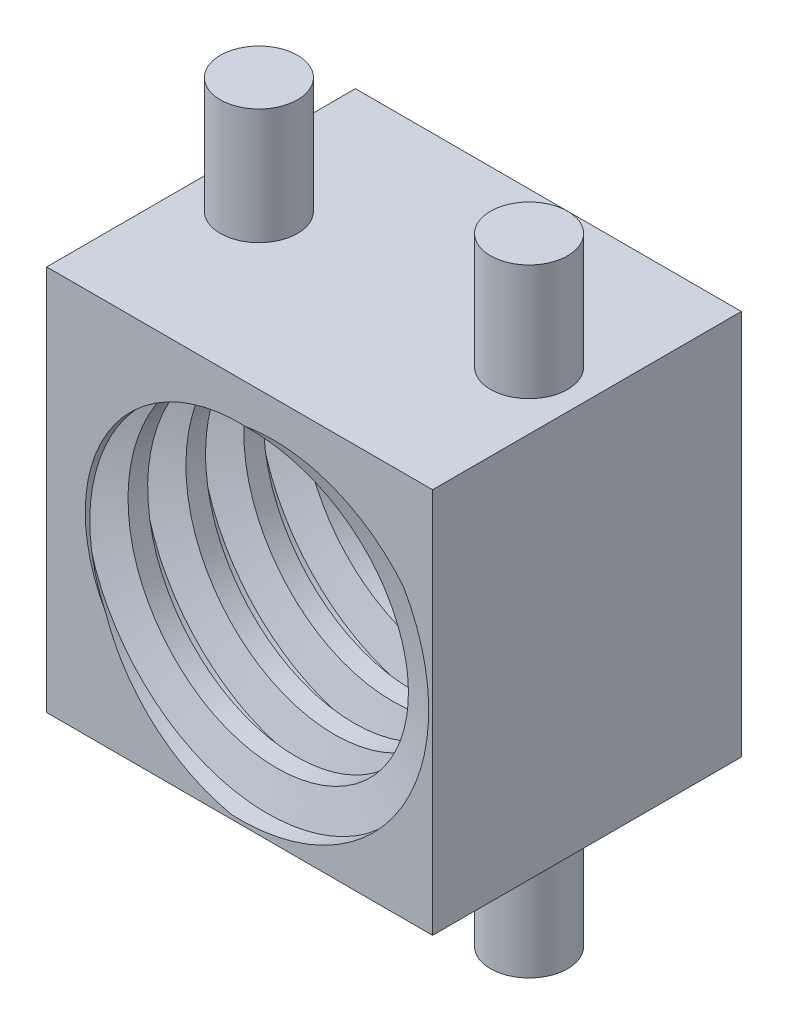
SolidWorks part; units mm, degrees
ref_plane "前视基准面" through (0, 0, 0) normal (0, 0, 1) x (1, 0, 0)
ref_plane "上视基准面" through (0, 0, 0) normal (0, 1, 0) x (1, 0, 0)
ref_plane "右视基准面" through (0, 0, 0) normal (1, 0, 0) x (0, 0, -1)
sketch "草图1" plane through (0, 0, 0) normal (1, 0, 0) x (0, 0, -1)
  line L0 (0, 0) -> (-9.8508, 0) construction
  line L1 (-8, 5) -> (0, 5)
  line L2 (-8, 5) -> (-8, 4)
  line L3 (-8, 4) -> (0, 4)
  line L4 (0, 5) -> (0, 4)
  dimension "bm" = 8
  dimension "d0" = 8
  dimension "dm" = 10
revolve "旋转1" add sketch "草图1" angle 360 about L0
sketch "草图2" plane through (0, 0, 0) normal (1, 0, 0) x (0, 0, -1)
  line L0 (0, 4) -> (0.9912, 4)
  line L1 (0, 4) -> (0.2412, 3.1) construction
  line L2 (0.2412, 3.1) -> (0.75, 3.1) construction
  line L3 (0.75, 3.1) -> (0.9912, 4) construction
  line L4 (-8, 4) -> (0, 4) construction
  line L5 (-8, 4) -> (0, 4) construction
  line L6 (0.75, 4.9) -> (0.9912, 4)
  line L7 (0.2412, 4.9) -> (0.75, 4.9)
  line L8 (0, 4) -> (0.2412, 4.9)
  dimension "t1" = 0.2412
  dimension "t2" = 0.5088
  dimension "p1" = 0.9912
  dimension "d1" = 3.1
sketch "草图3" plane through (0, 0, 0) normal (0, 0, 1) x (1, 0, 0)
  circle A0 centre (0, 0) radius 4
curve "螺旋线/涡状线1" pitch 1.5 height 16 radius 4 centre (0, 0, 0) axis (0, 0, 1) start towards (0, 1, 0) parameters "p"=1.5
sweep "切除-扫描1" cut profiles "草图2" path "螺旋线/涡状线1" align with end faces yes
sketch "草图4" plane through (0, 0, 0) normal (0, 0, 1) x (1, 0, 0)
  line L1 (-5, 5) -> (5, 5)
  line L2 (-5, 5) -> (-5, -5)
  line L3 (-5, -5) -> (5, -5)
  line L4 (5, 5) -> (5, -5)
  line L5 (-5, 5) -> (5, -5) construction
  line L6 (-5, -5) -> (5, 5) construction
  circle A0 centre (0, 0) radius 5
extrude "凸台-拉伸1" add sketch "草图4" along normal up to surface (8 mm away) contours A0 L2 L3 | A0 L1 L2 | A0 L4 L1 | A0 L3 L4 region at (-3.8832, 3.8832, 0) region at (3.8832, 3.8832, 0) region at (-3.8832, -3.8832, 0) region at (3.8832, -3.8832, 0) up to face at (-5, 0, 8)
sketch "草图5" plane through (0, 5, 0) normal (0, 1, 0) x (1, 0, 0)
  circle A0 centre (-3.5, -4) radius 1
  circle A1 centre (3.5, -4) radius 1
  dimension "D1" = 2
  dimension "D2" = 2
  dimension "D3" = 7
  dimension "D4" = 3.5
extrude "凸台-拉伸2" add sketch "草图5" along normal blind 3
mirror "镜向1" about plane through (0, 0, 0) normal (0, 1, 0) of "凸台-拉伸2"
equation "\"p1@草图2\" = \"t1@草图2\" * 2 + \"t2@草图2\""
equation "\"p@螺旋线/涡状线1\" =  \"p1@草图2\" + \"t2@草图2\""
equation "\"n@螺旋线/涡状线1\" = \"bm@草图1\" / \"p@螺旋线/涡状线1\"*2"
